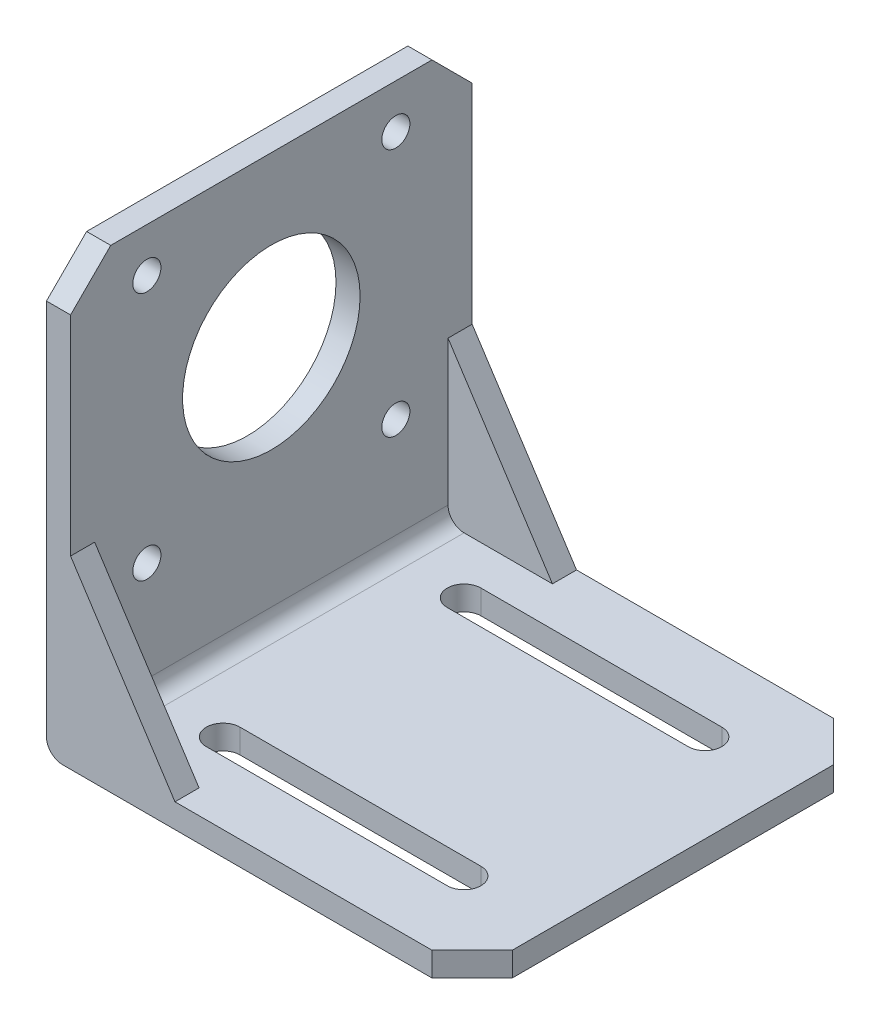
SolidWorks part; units mm, degrees
ref_plane "前视基准面" through (0, 0, 0) normal (0, 0, 1) x (1, 0, 0)
ref_plane "上视基准面" through (0, 0, 0) normal (0, 1, 0) x (1, 0, 0)
ref_plane "右视基准面" through (0, 0, 0) normal (1, 0, 0) x (0, 0, -1)
sketch "草图1" plane through (0, 0, 0) normal (0, 1, 0) x (1, 0, 0)
  line L1 (-26.5, -25) -> (26.5, -25)
  line L2 (-26.5, -25) -> (-26.5, 25)
  line L3 (-26.5, 25) -> (26.5, 25)
  line L4 (26.5, -25) -> (26.5, 25)
  line L5 (-26.5, -25) -> (26.5, 25) construction
  line L6 (-26.5, 25) -> (26.5, -25) construction
  point P0 (0, 0)
  dimension "D1" = 53
  dimension "D2" = 50
extrude "凸台-拉伸1" add sketch "草图1" along normal blind 3
chamfer "倒角1" distance 5 angle 45 2 edges at (26.5, 1.5, -25) (26.5, 1.5, 25)
sketch "草图2" plane through (0, 3, 0) normal (0, 1, 0) x (1, 0, 0)
  line L0 (-14.5, 15) -> (15.5, 15) construction
  line L1 (-14.5, 17.1) -> (15.5, 17.1)
  line L2 (-14.5, 12.9) -> (15.5, 12.9)
  line L3 (-14.5, -15) -> (15.5, -15) construction
  line L4 (-14.5, -12.9) -> (15.5, -12.9)
  line L5 (-14.5, -17.1) -> (15.5, -17.1)
  line L6 (26.5, -20) -> (26.5, 20) construction
  arc A0 (-14.5, 17.1) -> (-14.5, 12.9) centre (-14.5, 15) ccw
  arc A1 (15.5, 12.9) -> (15.5, 17.1) centre (15.5, 15) ccw
  arc A2 (-14.5, -12.9) -> (-14.5, -17.1) centre (-14.5, -15) ccw
  arc A3 (15.5, -17.1) -> (15.5, -12.9) centre (15.5, -15) ccw
  point P2 (0.5, 15)
  point P7 (0.5, -15)
  dimension "D1" = 30
  dimension "D2" = 30
  dimension "D3" = 30
  dimension "D4" = 15
  dimension "D5" = 11
  dimension "D6" = 4.2
  dimension "D7" = 4.2
extrude "切除-拉伸1" cut sketch "草图2" against normal up to next
sketch "草图3" plane through (0, 3, 0) normal (0, 1, 0) x (1, 0, 0)
  line L0 (-26.5, -25) -> (21.5, -25) construction
  line L1 (-26.5, 25) -> (-23.5, 25)
  line L2 (-26.5, 25) -> (-26.5, -25)
  line L3 (-26.5, -25) -> (-23.5, -25)
  line L4 (-23.5, 25) -> (-23.5, -25)
  dimension "D1" = 3
extrude "凸台-拉伸2" add sketch "草图3" along normal blind 51
fillet "圆角1" radius 2 2 edges at (-26.5, 0, 0) (-23.5, 3, 0)
sketch "草图6" plane through (0, 0, 25) normal (0, 0, 1) x (1, 0, 0)
  line L0 (-23.5, 23) -> (-10.5, 3)
  line L1 (-23.5, 54) -> (-23.5, 5) construction
  line L2 (-21.5, 3) -> (21.5, 3) construction
  dimension "D1" = 20
  dimension "D2" = 13
rib "筋1" sketch "草图6" sketch "草图6" thickness 3 extrusion direction parallel to sketch draft on no parameters "D1"=3
sketch "草图8" plane through (0, 0, -25) normal (0, 0, -1) x (-1, 0, 0)
  line L0 (10.5, 3) -> (23.5, 23)
  line L1 (-21.5, 3) -> (21.5, 3) construction
  line L2 (23.5, 54) -> (23.5, 5) construction
  line L3 (10.5, 3) -> (21.5, 3) construction
  line L4 (23.5, 5) -> (23.5, 23) construction
  dimension "D1" = 20
  dimension "D2" = 13
rib "筋3" sketch "草图8" sketch "草图8" thickness 3 extrusion direction parallel to sketch draft on no parameters "D1"=3
chamfer "倒角2" distance 5 angle 45 2 edges at (-25, 54, -25) (-25, 54, 25)
sketch "草图9" plane through (-23.5, 0, 0) normal (1, 0, 0) x (0, 0, -1)
  line L0 (-20, 54) -> (20, 54) construction
  line L1 (25, 49) -> (25, 23) construction
  circle A0 centre (0, 33) radius 11.05
  dimension "D1" = 22.1
  dimension "D2" = 21
  dimension "D3" = 25
extrude "切除-拉伸2" cut sketch "草图9" against normal up to next
hole_wizard "Ø3.5 (3.5) 直径孔1" positions "草图10" profile "草图11" hole size "Ø3.5" standard "GB" end condition up to next
sketch "草图10" plane through (-23.5, 0, 0) normal (1, 0, 0) x (0, 0, -1)
  line L0 (-25, 49) -> (-25, 23) construction
  line L1 (-20, 54) -> (20, 54) construction
  point P0 (-15.5, 48.5)
  point P2 (-15.5, 17.5)
  point P4 (15.5, 17.5)
  point P6 (15.5, 48.5)
  dimension "D1" = 31
  dimension "D2" = 9.5
  dimension "D3" = 31
  dimension "D4" = 5.5
sketch "草图11" plane through (-23.5, 48.5, 15.5) normal (0, 1, 0) x (0, 0, -1)
  line L0 (0, 0) -> (0, 3)
  line L1 (0, 3) -> (1.75, 3)
  line L2 (1.75, 3) -> (1.75, 0)
  line L5 (1.75, 0) -> (0, 0)
  line L11 (0, -6.35) -> (0, 107.95) construction
  dimension "通孔孔直径" = 3.5
  dimension "通孔孔深度" = 3
